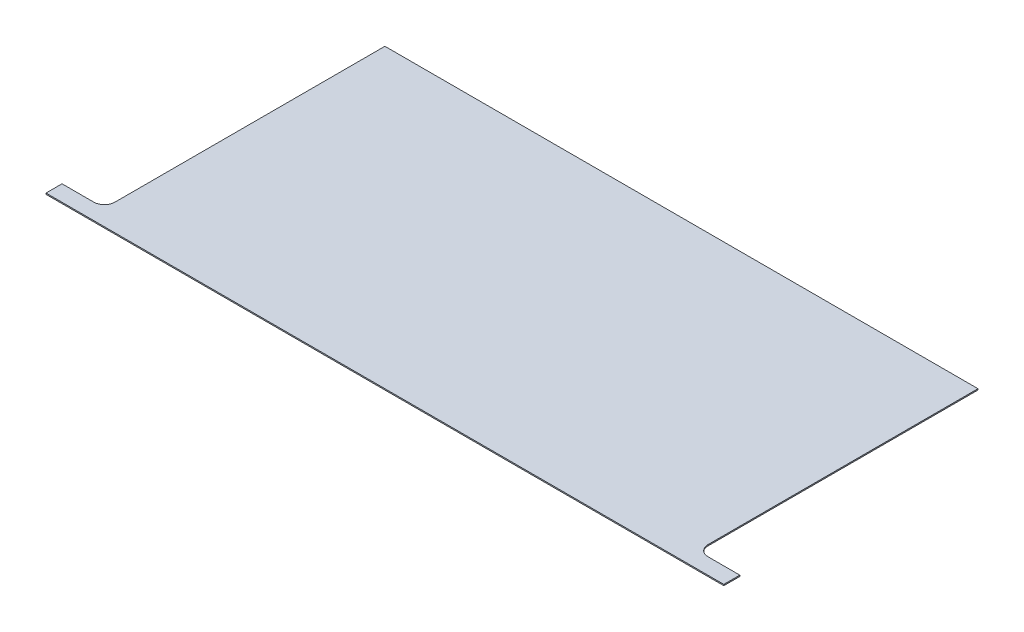
SolidWorks part; units mm, degrees
ref_plane "Front Plane" through (0, 0, 0) normal (0, 0, 1) x (1, 0, 0)
ref_plane "Top Plane" through (0, 0, 0) normal (0, 1, 0) x (1, 0, 0)
ref_plane "Right Plane" through (0, 0, 0) normal (1, 0, 0) x (0, 0, -1)
sketch "Sketch1" plane through (0, 0, 0) normal (0, 1, 0) x (1, 0, 0)
  line L0 (12.7, 88.9) -> (12.7, 4.8)
  line L1 (12.7, 0) -> (190.5, 0)
  line L2 (12.7, 4.8) -> (0, 4.8)
  line L3 (12.7, 88.9) -> (190.5, 88.9)
  line L4 (0, 4.8) -> (0, 0)
  line L5 (0, 0) -> (12.7, 0)
  line L6 (190.5, 88.9) -> (190.5, 4.8)
  line L7 (190.5, 4.8) -> (203.2, 4.8)
  line L8 (203.2, 4.8) -> (203.2, 0)
  line L9 (203.2, 0) -> (190.5, 0)
  dimension "D1" = 88.9
  dimension "D2" = 4.8
  dimension "D3" = 12.7
  dimension "D4" = 203.2
  dimension "D5" = 84.1
extrude "Boss-Extrude1" add sketch "Sketch1" along normal blind 0.3556
ref_plane "Center of Card" through (101.6, 0, 0) normal (-1, 0, 0) x (0, 0, 1)
sketch "Paper Size Check" plane through (0, 0, 0) normal (0, 1, 0) x (1, 0, 0)
  line L0 (6.35, 263.0125) -> (196.85, 263.0125) construction
  line L1 (-6.35, -3.6875) -> (209.55, -3.6875) construction
  line L2 (-6.35, -3.6875) -> (-6.35, 275.7125) construction
  line L3 (-6.35, 275.7125) -> (209.55, 275.7125) construction
  line L4 (209.55, -3.6875) -> (209.55, 275.7125) construction
  line L5 (196.85, 9.0125) -> (196.85, 263.0125) construction
  line L6 (6.35, 9.0125) -> (196.85, 9.0125) construction
  line L7 (6.35, 9.0125) -> (6.35, 263.0125) construction
  line L9 (6.35, 136.0125) -> (196.85, 136.0125) construction
  line L10 (101.6, 0.1956) -> (101.6, -0.1956) construction
  point P10 (101.6, 136.0125)
  dimension "D1" = 215.9
  dimension "D2" = 279.4
  dimension "D3" = 12.7
fillet "Fillet1" [suppressed] radius 6.35
fillet "Fillet2" [suppressed] radius 6.35
fillet "Fillet3" radius 3.175 2 edges at (12.7, 0.1778, -4.8) (190.5, 0.1778, -4.8)
ref_plane "Middle of Tab Plane" through (0, 0, -2.4) normal (0, 0, 1) x (1, 0, 0)
ref_plane "Plane2" through (0, 0.1778, 0) normal (0, 1, 0) x (1, 0, 0)
ref_axis "Axis1" through (10.0012, 0.1778, -2.4) along (-1, 0, 0)
